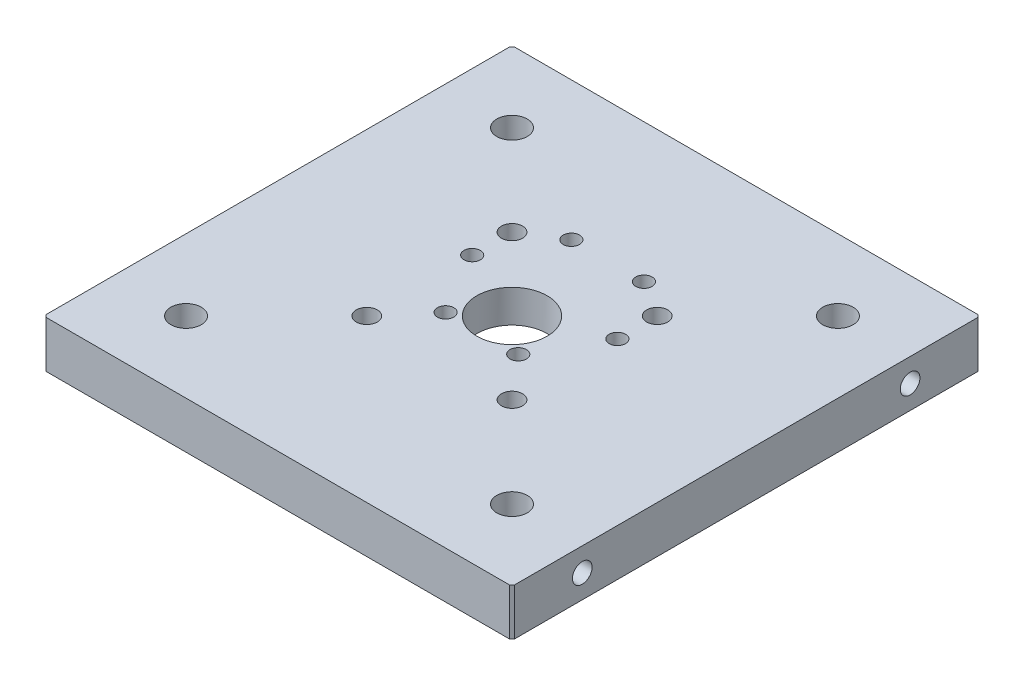
SolidWorks part; units mm, degrees
material "6061 Alloy"
ref_plane "Front Plane" through (0, 0, 0) normal (0, 0, 1) x (1, 0, 0)
ref_plane "Top Plane" through (0, 0, 0) normal (0, 1, 0) x (1, 0, 0)
ref_plane "Right Plane" through (0, 0, 0) normal (1, 0, 0) x (0, 0, -1)
sketch "Sketch1" plane through (0, 0, 0) normal (0, 1, 0) x (1, 0, 0)
  line L0 (0, 50) -> (0, -50) construction
  line L1 (-50, 50) -> (50, 50)
  line L2 (-50, 50) -> (-50, -50)
  line L3 (-50, -50) -> (50, -50)
  line L4 (50, 50) -> (50, -50)
  line L5 (-50, 0) -> (50, 0) construction
  point P8 (0, 0)
  dimension "D1" = 100
  dimension "D2" = 0
extrude "Boss-Extrude1" add sketch "Sketch1" along normal blind 5 and the other way blind 5
sketch "Sketch2" plane through (0, 5, 0) normal (0, 1, 0) x (1, 0, 0)
  line L1 (0, 50) -> (0, -50) construction
  line L2 (50, 50) -> (-50, 50) construction
  line L3 (-50, -50) -> (50, -50) construction
  line L4 (-50, 0) -> (50, 0) construction
  line L5 (-50, 50) -> (-50, -50) construction
  line L6 (50, -50) -> (50, 50) construction
  circle A0 centre (0, 0) radius 7.5
  circle A1 centre (-34.7985, 34.7985) radius 3.25
  circle A2 centre (34.7985, 34.7985) radius 3.25
  circle A3 centre (34.7985, -34.7985) radius 3.25
  circle A4 centre (-34.7985, -34.7985) radius 3.25
  dimension "D1" = 6.5
  dimension "D3" = 15
  dimension "D2" = 34.7985
  dimension "D4" = 34.7985
  dimension "D5" = 34.7985
  dimension "D6" = 50
  dimension "D7" = 50
extrude "Cut-Extrude1" cut sketch "Sketch2" against normal blind 12.7
hole_wizard "Tap Drill for M5x0.8 Tap1" positions "Sketch9" profile "Sketch10" hole size "M5x0.8" standard "ANSI Metric"
sketch "Sketch9" plane through (-50, 0, 0) normal (-1, 0, 0) x (0, 0, 1)
  line L0 (-50, -5) -> (50, -5) construction
  line L1 (-50, 5) -> (-50, -5) construction
  line L2 (50, 5) -> (50, -5) construction
  point P0 (-35, 0)
  point P2 (35, 0)
  dimension "D1" = 5
  dimension "D2" = 15
  dimension "D3" = 5
  dimension "D4" = 15
sketch "Sketch10" plane through (-50, 0, -35) normal (0, 1, 0) x (0, 0, 1)
  line L0 (0, 0) -> (0, 11.2618)
  line L1 (0, 11.2618) -> (2.1, 10)
  line L2 (2.1, 10) -> (2.1, 0)
  line L5 (2.1, 0) -> (0, 0)
  line L10 (0, 11.2618) -> (-2.1, 10) construction
  line L11 (0, -6.35) -> (0, 107.95) construction
  dimension "Hole Dia." = 4.2
  dimension "Hole Depth" = 10
  dimension "Drill Angle" = 118
sketch "Sketch11" plane through (0, -5, 0) normal (0, -1, 0) x (1, 0, 0)
  circle A0 centre (0, 0) radius 37.5
  dimension "D1" = 75
extrude "Cut-Extrude2" cut sketch "Sketch11" against normal blind 3
chamfer "Chamfer1" distance 0.5 angle 45 4 edges at (50, 0, -50) (50, 0, 50) (-50, 0, 50) (-50, 0, -50)
ref_plane "Plane1" through (0, 0, 0) normal (-1, 0, 0) x (0, 0, 1)
mirror "Mirror1" about plane through (0, 0, 0) normal (-1, 0, 0) of "Tap Drill for M5x0.8 Tap1"
sketch "Sketch12" plane through (0, 5, 0) normal (0, 1, 0) x (1, 0, 0)
  line L0 (0, 50) -> (0, -50) construction
  circle A0 centre (-15.5, 7) radius 1.75
  circle A1 centre (15.5, 7) radius 1.75
  circle A3 centre (-7.75, 20.4234) radius 1.75
  circle A4 centre (7.75, 20.4234) radius 1.75
  circle A5 centre (15.5, 7) radius 1.75
  circle A6 centre (7.75, -6.4234) radius 1.75
  circle A7 centre (-7.75, -6.4234) radius 1.75
  point P23 (0, 7)
  dimension "D1" = 7
  dimension "D3" = 6
  dimension "D4" = 3.5
  dimension "D2" = 15.5
extrude "Cut-Extrude3" cut sketch "Sketch12" against normal through all contours A4 | A3 | A1 | A6 | A7 | A0 region at (7.75, 5, -20.4234)
sketch "Sketch13" plane through (0, 5, 0) normal (0, 1, 0) x (1, 0, 0)
  circle A0 centre (0, 0) radius 21.9203
  circle A1 centre (-15.5, -15.5) radius 2.25
  circle A2 centre (-15.5, 15.5) radius 2.25
  circle A3 centre (15.5, 15.5) radius 2.25
  circle A4 centre (15.5, -15.5) radius 2.25
  point P13 (0, 0)
  dimension "D1" = 15.5
  dimension "D4" = 4.5
  dimension "D2" = 15.5
  dimension "D3" = 4
extrude "Cut-Extrude4" cut sketch "Sketch13" against normal blind 10 contours A2 | A3 | A4 | A1
